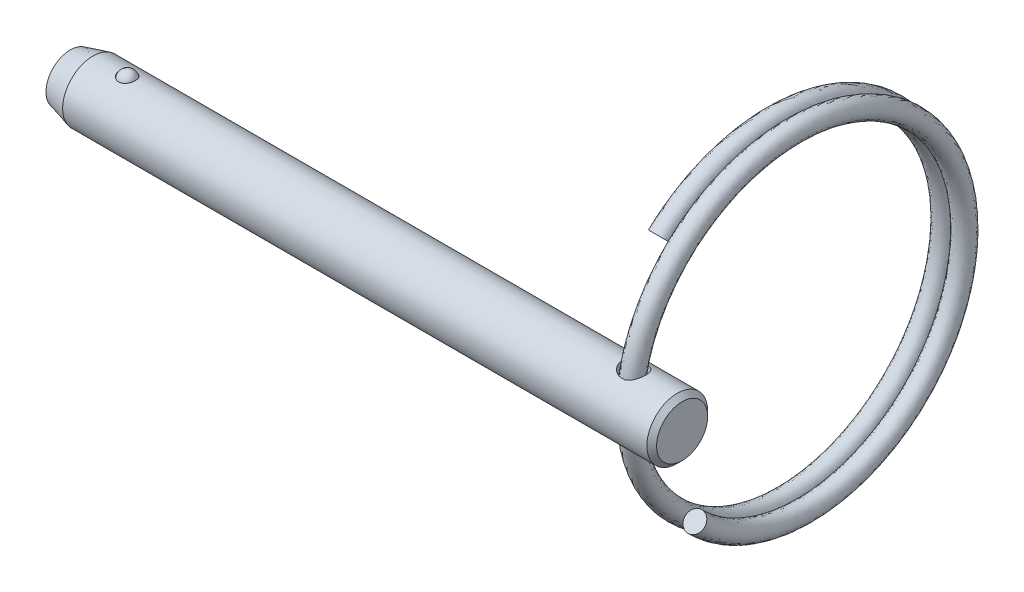
SolidWorks part; units mm, degrees
ref_plane "Front" through (0, 0, 0) normal (0, 0, 1) x (1, 0, 0)
ref_plane "Top" through (0, 0, 0) normal (0, 1, 0) x (1, 0, 0)
ref_plane "Right" through (0, 0, 0) normal (1, 0, 0) x (0, 0, -1)
sketch "Sketch1" plane through (0, 0, 0) normal (0, 0, 1) x (1, 0, 0)
  line L0 (23.9649, 2.0003) -> (23.5839, 2.3813)
  line L1 (23.5839, 2.3813) -> (23.9649, 2.3813) construction
  line L4 (23.9649, 2.0003) -> (23.9649, 0)
  line L5 (23.9649, 2.3813) -> (23.9649, 2.0003) construction
  line L16 (23.5839, 2.3813) -> (-22.1875, 2.3813)
  line L17 (-23.9649, 2.3813) -> (-23.9649, 1.905) construction
  line L19 (-22.1875, 2.3813) -> (-23.9649, 2.3813) construction
  line L22 (-23.9649, -2.3813) -> (-22.1875, -2.3812) construction
  line L23 (-19.4975, 2.1431) -> (-19.4975, -2.1431) construction
  line L24 (-23.9649, 0) -> (23.9649, 0)
  line L27 (23.9649, 0) -> (25.9652, 0) construction
  line L29 (-23.9649, 0) -> (-23.9649, -1.905) construction
  line L36 (19.2151, 0) -> (19.2151, 2.3813) construction
  line L37 (-23.9649, 1.905) -> (-23.9649, 0)
  line L38 (-22.1875, -2.3812) -> (23.9649, -2.3813) construction
  line L39 (-23.9649, -1.905) -> (-23.9649, -2.3813) construction
  line L40 (-22.1875, 2.3813) -> (-23.9649, 1.905)
  line L42 (-22.1875, -2.3812) -> (-23.9649, -1.905) construction
  line L43 (-22.1875, 2.3813) -> (-22.1875, -2.3812) construction
  circle A2 centre (-19.4975, 2.1431) radius 0.6572 construction
  point P35 (-18.8849, 2.3813)
  dimension "A1" = 15
revolve "Revolve1" add sketch "Sketch1" angle 360 about L27
sketch "Sketch2" plane through (0, 0, 0) normal (0, 0, 1) x (1, 0, 0)
  line L0 (-18.8148, 2.1431) -> (-20.1801, 2.1431)
  line L1 (-19.4975, 2.8003) -> (-19.4975, 2.8257) construction
  line L2 (-18.8148, 2.1431) -> (-17.4496, 2.1431) construction
  circle A0 centre (-19.4975, 2.1431) radius 0.6572 construction
  circle A1 centre (-19.4975, 2.1431) radius 0.6572 construction
  arc A2 (-20.1801, 2.1431) -> (-18.8148, 2.1431) centre (-19.4975, 2.1431) cw
  dimension "D1" = 0.0254
revolve "Cut-Revolve1" cut sketch "Sketch2" angle 360 about L2
sketch "Sketch3" plane through (0, 0, 0) normal (0, 0, 1) x (1, 0, 0)
  line L0 (-18.8402, 2.1431) -> (-20.1547, 2.1431)
  line L1 (-18.8402, 2.1431) -> (-17.5258, 2.1431) construction
  circle A0 centre (-19.4975, 2.1431) radius 0.6572 construction
  arc A1 (-18.8402, 2.1431) -> (-20.1547, 2.1431) centre (-19.4975, 2.1431) ccw
revolve "Revolve2" add sketch "Sketch3" angle 360 about L1
sketch "Sketch4" plane through (0, 0, 0) normal (0, 0, 1) x (1, 0, 0)
  line L1 (20.1676, -2.3812) -> (21.1201, -2.3812)
  line L2 (20.1676, -2.3812) -> (20.1676, 2.3812)
  line L3 (20.1676, 2.3812) -> (21.1201, 2.3812)
  line L4 (21.1201, -2.3812) -> (21.1201, 2.3812)
  line L5 (20.1676, -2.3812) -> (20.1676, -3.3337) construction
  line L6 (21.1201, 2.3812) -> (23.9649, 2.3813) construction
  line L8 (19.2151, -2.3812) -> (19.2151, 2.3812) construction
  line L9 (19.2151, 0) -> (20.1676, 0) construction
  line L11 (20.1676, 0) -> (21.1201, 0) construction
  line L12 (23.5839, 2.3813) -> (-22.1875, 2.3813) construction
  line L14 (-22.1875, -2.3812) -> (23.9649, -2.3812) construction
  dimension "D1" = 1.905
revolve "Cut-Revolve2" cut sketch "Sketch4" angle 360 about L2
sketch "Sketch5" plane through (0, 0, 0) normal (0, 0, 1) x (1, 0, 0)
  line L0 (0, 0) -> (19.2856, 0) construction
  line L1 (19.2856, 0) -> (19.2856, 2.3813) construction
  line L2 (23.5839, 2.3813) -> (-22.1875, 2.3813) construction
  line L3 (32.7476, 0) -> (46.2096, 0) construction
  line L4 (21.1201, 2.3812) -> (21.0496, 2.3813) construction
  line L5 (20.1676, 2.3812) -> (21.1201, 2.3812) construction
  line L6 (19.4979, 2.3812) -> (19.4979, -2.3812) construction
  line L7 (19.2856, 2.3813) -> (19.2151, 2.3813) construction
  line L8 (20.1676, -2.3812) -> (21.1201, -2.3812) construction
  line L9 (19.4979, -2.3812) -> (21.1201, -2.3812) construction
  line L10 (19.2856, 0) -> (32.7476, 0) construction
  line L12 (21.0496, 2.3813) -> (19.4979, 2.3812) construction
  line L13 (32.7476, 11.938) -> (32.7476, 13.462) construction
  circle A0 centre (32.7476, 0) radius 13.462
  circle A1 centre (32.7476, 0) radius 11.938 construction
  circle A2 centre (32.7476, 0) radius 12.7 construction
  point P26 (32.7476, 12.7)
curve "Helix/Spiral1" pitch 1.5494 height 1.3557 radius 13.462 left hand yes centre (32.7476, 0, 0) axis (0, 0, -1) start towards (1, 0, 0)
sketch "Sketch6" plane through (114.0038, 0, 0) normal (0, 1, 0) x (0, 0, -1)
  line L0 (0, 93.1942) -> (0, 93.9562) construction
  line L1 (0, 93.9562) -> (0, 94.7182) construction
  circle A0 centre (0, 93.9562) radius 0.762
  dimension "D1" = 1.524
sketch "Sketch7" plane through (0, 0, 0) normal (0, 0, 1) x (1, 0, 0)
  circle A0 centre (32.7476, 0) radius 13.462 construction
  circle A1 centre (32.7476, 0) radius 13.462
curve "Helix/Spiral2" pitch 1.5494 height 1.3557 radius 13.462 left hand yes centre (32.7476, 0, 0) axis (0, 0, 1) start towards (1, 0, 0)
sweep "Sweep1" add profiles "Sketch6" path "Helix/Spiral1"
sweep "Sweep2" add profiles "Sketch6<2>" path "Helix/Spiral2"
sketch "Sketch6<2>" plane through (114.0038, 0, 0) normal (0, 1, 0) x (0, 0, -1) same geometry as "Sketch6"
move or copy body "Body-Move/Copy1" bodies to move or copy 141 copy no rotation origin (32.7476, 0, 0) rotation axis (0, 1, 0) rotation angle 90
move or copy body "Body-Move/Copy2" bodies to move or copy 142 copy no translate (-12.4856, 0, -12.3266)
equation "\"D12@Sketch1\"=\"A@Sketch1\" * 0.80"
equation "\"D2@Sketch1\"=\"A@Sketch1\" * 0.9"
equation "\"D1@Sketch4\" = \"A@Sketch1\" / 2.5"
equation "\"Ring OD@Sketch5\" = \"R Ring Dia@Sketch5\" * 0.06"
equation "\"D4@Helix/Spiral1\"=\"Ring OD@Sketch5\" + 0.001"
equation "\"D1@Sketch6\"=\"Ring OD@Sketch5\""
equation "\"D4@Helix/Spiral2\" = \"D4@Helix/Spiral1\""
equation "\"D5@Helix/Spiral2\" = \"D5@Helix/Spiral1\""
